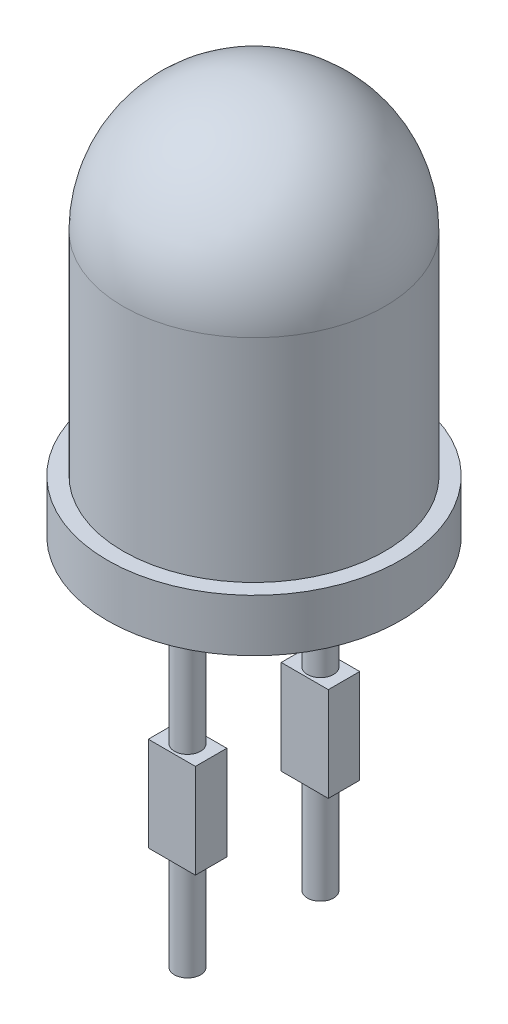
SolidWorks part; units mm, degrees
ref_plane "Front Plane" through (0, 0, 0) normal (0, 0, 1) x (1, 0, 0)
ref_plane "Top Plane" through (0, 0, 0) normal (0, 1, 0) x (1, 0, 0)
ref_plane "Right Plane" through (0, 0, 0) normal (1, 0, 0) x (0, 0, -1)
sketch "Sketch1" plane through (0, 0, 0) normal (1, 0, 0) x (0, 0, -1)
  line L0 (0, 4.525) -> (0, -10.9525) construction
  line L1 (-2.5, 2.025) -> (-2.5, -2.025)
  line L2 (-2.5, -2.025) -> (-2.8, -2.025)
  line L3 (-2.8, -2.025) -> (-2.8, -3.025)
  line L4 (-2.8, -3.025) -> (0, -3.025)
  line L5 (0, 4.525) -> (-4.2269, 4.525) construction
  line L6 (0, 4.525) -> (0, -3.025)
  arc A0 (-2.5, 2.025) -> (0, 4.525) centre (0, 2.025) cw
  point P11 (-2.5, 0)
  dimension "D1" = 5
  dimension "D2" = 7.55
  dimension "D3" = 1
  dimension "D4" = 5.6
revolve "Revolve1" add sketch "Sketch1" angle 360 about L0
sketch "Sketch2" plane through (0, -3.025, 0) normal (0, -1, 0) x (1, 0, 0)
  line L0 (0, 0) -> (3.908, 0) construction
  circle A0 centre (0, 1.27) radius 0.25
  circle A1 centre (0, -1.27) radius 0.25
  dimension "D1" = 2.54
  dimension "D2" = 0.5
extrude "Boss-Extrude1" add sketch "Sketch2" along normal blind 11 separate body
sketch "Sketch3" plane through (0, 0, 0) normal (1, 0, 0) x (0, 0, -1)
  line L0 (1.27, -3.025) -> (1.27, -15.6133) construction
  line L1 (0.97, -5.825) -> (1.57, -5.825)
  line L2 (0.97, -5.825) -> (0.97, -7.625)
  line L3 (0.97, -7.625) -> (1.57, -7.625)
  line L4 (1.57, -5.825) -> (1.57, -7.625)
  line L5 (0.97, -5.825) -> (1.57, -7.625) construction
  line L6 (0.97, -7.625) -> (1.57, -5.825) construction
  line L7 (1.52, -3.025) -> (1.02, -3.025) construction
  line L8 (-2.8, -3.025) -> (2.8, -3.025) construction
  line L9 (0, 0) -> (0, -3.6509) construction
  line L10 (-0.97, -7.625) -> (-1.57, -7.625)
  line L11 (-1.57, -5.825) -> (-1.57, -7.625)
  line L12 (-0.97, -5.825) -> (-1.57, -5.825)
  line L13 (-0.97, -5.825) -> (-0.97, -7.625)
  point P0 (1.27, -6.725)
  dimension "D1" = 0.6
  dimension "D2" = 2.8
  dimension "D3" = 1.8
extrude "Boss-Extrude2" add sketch "Sketch3" along normal mid plane 0.9
sketch "Sketch4" plane through (0, 0, 0) normal (1, 0, 0) x (0, 0, -1)
  line L0 (-2.8, -3.025) -> (2.8, -3.025) construction
  line L1 (-3.8671, -9.525) -> (5.3561, -9.525)
  line L2 (-3.8671, -9.525) -> (-3.8671, -15.8944)
  line L3 (-3.8671, -15.8944) -> (5.3561, -15.8944)
  line L4 (5.3561, -9.525) -> (5.3561, -15.8944)
  dimension "D1" = 6.5
extrude "Cut-Extrude1" cut sketch "Sketch4" against normal through all both and the other way through all
